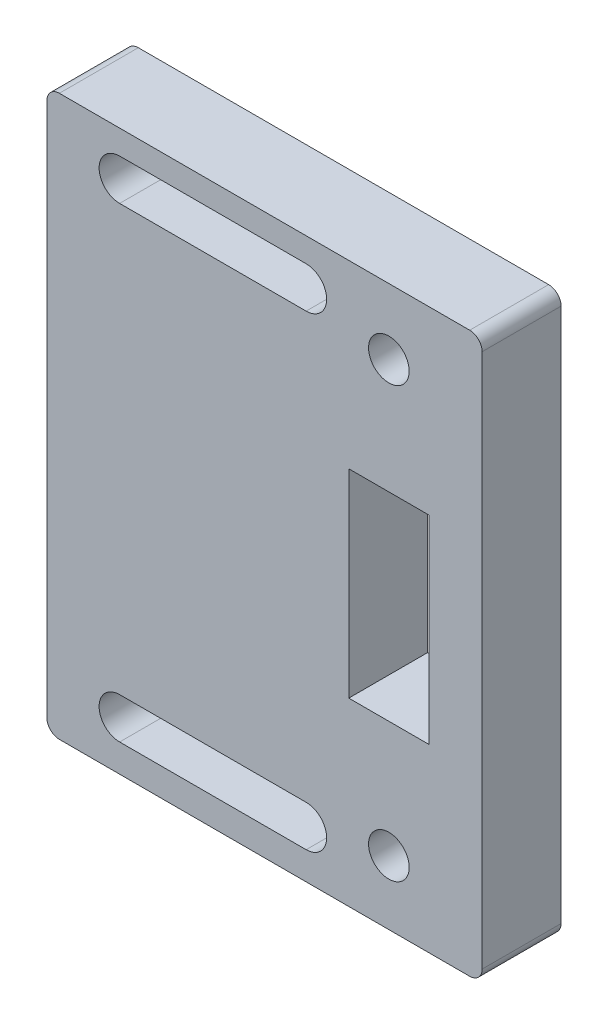
SolidWorks part; units mm, degrees
ref_plane "Front Plane" through (0, 0, 0) normal (0, 0, 1) x (1, 0, 0)
ref_plane "Top Plane" through (0, 0, 0) normal (0, 1, 0) x (1, 0, 0)
ref_plane "Right Plane" through (0, 0, 0) normal (1, 0, 0) x (0, 0, -1)
sketch "Sketch1" plane through (0, 0, 0) normal (0, 0, 1) x (1, 0, 0)
  line L0 (70, -45) -> (0, -45) construction
  line L1 (0, 0) -> (70, 0)
  line L2 (0, 0) -> (0, -90)
  line L3 (0, -90) -> (70, -90)
  line L4 (70, 0) -> (70, -90)
  line L5 (55, -45) -> (55, -29.025) construction
  line L6 (55, -29.025) -> (61.45, -29.025)
  line L7 (61.45, -29.025) -> (61.45, -60.975)
  line L8 (61.45, -60.975) -> (55, -60.975)
  line L9 (55, -60.975) -> (48.55, -60.975)
  line L10 (48.55, -60.975) -> (48.55, -29.025)
  line L11 (48.55, -29.025) -> (55, -29.025)
  line L12 (55, -45) -> (55, -60.975) construction
  line L13 (55, 0) -> (55, -13.25) construction
  line L14 (55, -90) -> (55, -79.56) construction
  dimension "D1" = 90
  dimension "D2" = 55
  dimension "D3" = 12.9
  dimension "D4" = 31.95
  dimension "D5" = 70
  dimension "D6" = 10.44
  dimension "D7" = 55
  dimension "D8" = 55
extrude "Boss-Extrude1" add sketch "Sketch1" along normal blind 12.7
sketch "Sketch4" plane through (0, 0, 0) normal (0, 0, -1) x (-1, 0, 0)
  line L0 (-55, -0.2792) -> (-55, -10.5796)
  line L2 (-55, -90) -> (-55, -79.6996)
  line L4 (-55, -79.6996) -> (-55, -10.5796) construction
  line L5 (0, 0) -> (0, -90) construction
  line L6 (0, -90) -> (-70, -90) construction
  line L9 (0, -90) -> (-70, -90) construction
  dimension "D1" = 55
  dimension "D2" = 10.3004
  dimension "D3" = 69.12
hole_wizard "CSK for 1/4 Flat Head Machine Screw1" positions "Sketch5" profile "Sketch6" countersink size "1/4" standard "ANSI Inch" end condition through all
sketch "Sketch5" plane through (0, 0, 0) normal (0, 0, -1) x (-1, 0, 0)
  point P0 (-55, -10.5796)
  point P3 (-55, -79.6996)
sketch "Sketch6" plane through (55, -10.5796, 0) normal (1, 0, 0) x (0, 1, 0)
  line L0 (0, 0) -> (0, 12.7)
  line L1 (0, 12.7) -> (3.2639, 12.7)
  line L2 (3.2639, 12.7) -> (3.2639, 3.6524)
  line L3 (3.2639, 3.6524) -> (6.4389, 0)
  line L5 (6.4389, 0) -> (0, 0)
  line L6 (-3.2639, 3.6524) -> (-6.4389, 0) construction
  line L11 (0, -6.35) -> (0, 107.95) construction
  dimension "Thru Hole Dia." = 6.5278
  dimension "Thru Hole Depth" = 12.7
  dimension "Near C'Sink Dia." = 12.8778
  dimension "Near C'Sink Angle" = 82
fillet "Fillet1" radius 2 4 edges at (0, 0, 6.35) (70, 0, 6.35) (0, -90, 6.35) (70, -90, 6.35)
sketch "Sketch7" plane through (0, 0, 0) normal (0, 0, -1) x (-1, 0, 0)
  line L0 (-41.6955, -85.5134) -> (-11.6955, -85.5134)
  line L1 (-11.6955, -78.9134) -> (-41.6955, -78.9134)
  line L2 (-11.6955, -78.9134) -> (-11.6955, -10.4934) construction
  line L3 (-11.6955, -10.4934) -> (-41.6955, -10.4934)
  line L4 (-11.6955, -3.8934) -> (-41.6955, -3.8934)
  arc A0 (-11.6955, -85.5134) -> (-11.6955, -78.9134) centre (-11.6955, -82.2134) ccw
  arc A1 (-41.6955, -78.9134) -> (-41.6955, -85.5134) centre (-41.6955, -82.2134) ccw
  arc A2 (-11.6955, -10.4934) -> (-11.6955, -3.8934) centre (-11.6955, -7.1934) ccw
  arc A3 (-41.6955, -3.8934) -> (-41.6955, -10.4934) centre (-41.6955, -7.1934) ccw
  dimension "D1" = 3.3
  dimension "D4" = 3.3
  dimension "D2" = 30
  dimension "D3" = 68.42
  dimension "D5" = 30
extrude "Cut-Extrude1" cut sketch "Sketch7" against normal through all contours A1 L0 A0 L1 | A3 L3 A2 L4
